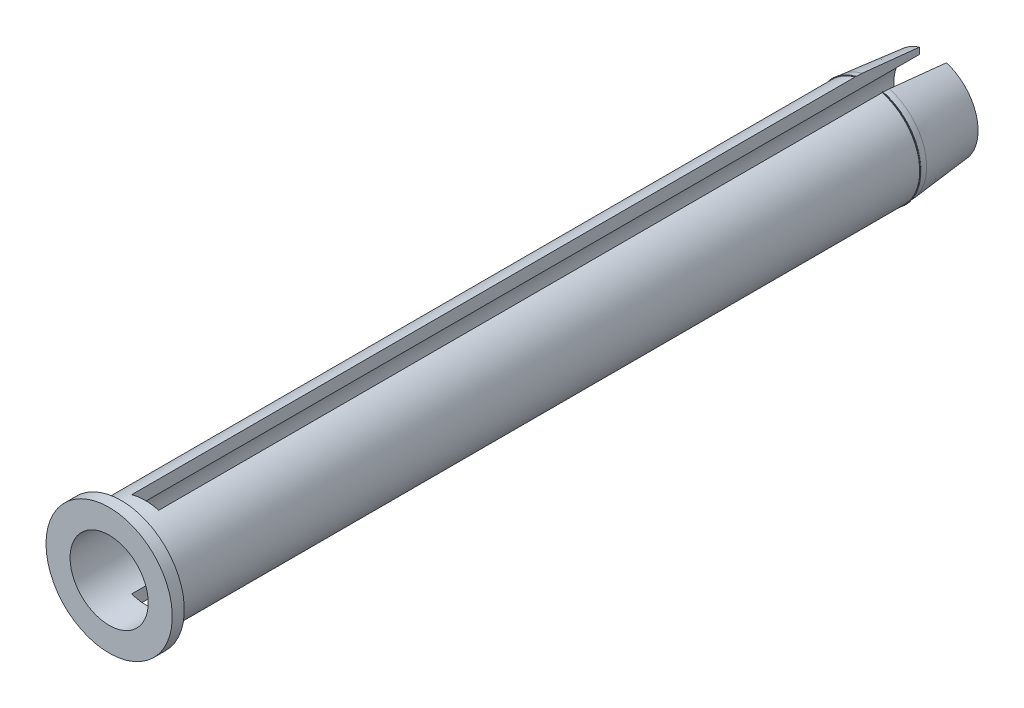
SolidWorks part; units mm, degrees
ref_plane "Alzado" through (0, 0, 0) normal (1, 0, 0) x (0, 1, 0)
ref_plane "Planta" through (0, 0, 0) normal (0, 0, 1) x (0, 1, 0)
ref_plane "Vista lateral" through (0, 0, 0) normal (0, 1, 0) x (-1, 0, 0)
sketch "Croquis1" plane through (0, 0, 0) normal (1, 0, 0) x (0, 1, 0)
  line L0 (6.5, -68.5) -> (6.5, 68.5)
  line L1 (6.5, 68.5) -> (10.5, 68.5)
  line L2 (10.5, 68.5) -> (10.5, 66.5)
  line L3 (10.5, 66.5) -> (8.5, 66.5)
  line L4 (8.5, 66.5) -> (8.5, -68.5)
  line L8 (0, 0) -> (0, 4.1277) construction
  line L9 (8.5, -68.5) -> (6.5, -68.5)
  point P3 (6.5, 0)
  dimension "D1" = 2
  dimension "D4" = 2
  dimension "D5" = 2
  dimension "D2" = 135
  dimension "D3" = 17
revolve "Revolución1" add sketch "Croquis1" angle 360 about L8
chamfer "Chaflán2" distance 10 distance2 1 1 edges at (-8.5, 0, -68.5) first distance on face at (-8.5, 0, 66.5)
fillet "Redondeo1" radius 10 1 edges at (-8.5, 0, -58.5)
sketch "Croquis3" plane through (0, 0, -68.5) normal (0, 0, -1) x (1, 0, 0)
  circle A1 centre (0, 0) radius 8.5 construction
  circle A2 centre (0, 0) radius 8.6
  circle A4 centre (0, 0) radius 8.5
  dimension "D1" = 0.1
extrude "Saliente-Extruir1" add sketch "Croquis3" against normal blind 0.2 from offset 10.5 contours A2 region at (-8.5757, 0, -68.5) offset against normal yes
sketch "Croquis2" plane through (0, 0, -68.5) normal (0, 0, -1) x (1, 0, 0)
  line L1 (-2.25, -10.2561) -> (2.25, -10.2561)
  line L2 (-2.25, -10.2561) -> (-2.25, 10.2561)
  line L3 (-2.25, 10.2561) -> (2.25, 10.2561)
  line L4 (2.25, -10.2561) -> (2.25, 10.2561)
  line L5 (-2.25, -10.2561) -> (2.25, 10.2561) construction
  line L6 (-2.25, 10.2561) -> (2.25, -10.2561) construction
  circle A0 centre (0, 0) radius 10.5 construction
  point P0 (0, 0)
  dimension "D1" = 4.5
extrude "Cortar-Extruir1" cut sketch "Croquis2" against normal offset from surface (131 mm away) 4 up to face at (-10.5, 0, 66.5)
chamfer "Chaflán3" distance 0.1 distance2 0.1 2 edges at (8.6, 0, -58) (-8.6, 0, -58)
fillet "Redondeo2" radius 0.05 4 edges at (8.6, 0, -57.8) (8.6, 0, -57.9) (-8.6, 0, -57.9) (-8.6, 0, -57.8)
equation "\"D5@Croquis1\"=\"D4@Croquis1\""
